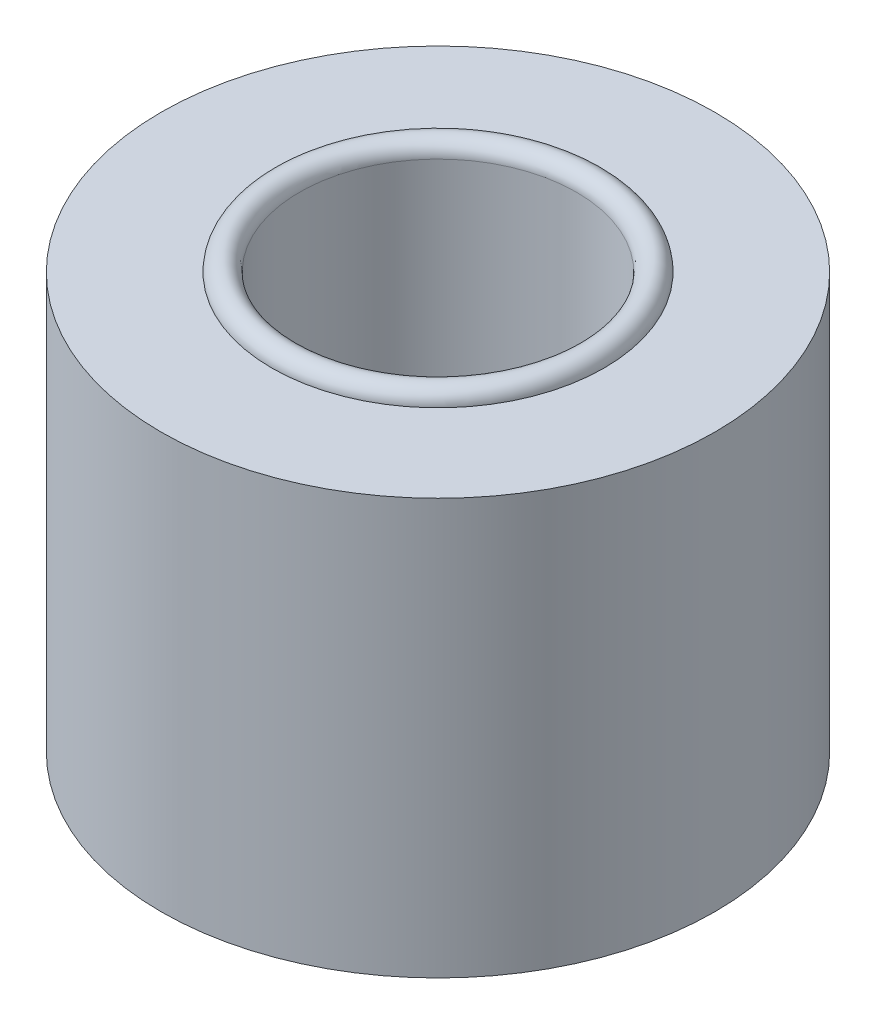
SolidWorks part; units mm, degrees
note: The reader was unsure of these and kept them because the rebuilt part matched: shared geometry of "Sketch2<2>".
ref_plane "Front Plane" through (0, 0, 0) normal (0, 0, 1) x (1, 0, 0)
ref_plane "Top Plane" through (0, 0, 0) normal (0, 1, 0) x (1, 0, 0)
ref_plane "Right Plane" through (0, 0, 0) normal (1, 0, 0) x (0, 0, -1)
sketch "Profile Sketch" plane through (0, 0, 0) normal (0, 1, 0) x (1, 0, 0)
  circle A0 centre (0, 0) radius 20
  circle A1 centre (0, 0) radius 10
  dimension "D1" = 40
  dimension "D2" = 20
extrude "Profile Extrude" add sketch "Profile Sketch" along normal blind 30
sketch "Ring Lip Profile" plane through (0, 30, 0) normal (0, 1, 0) x (1, 0, 0)
  circle A0 centre (0, 0) radius 10
  circle A1 centre (0, 0) radius 12
  circle A2 centre (0, 0) radius 10 construction
  dimension "D1" = 2
extrude "Top Ring Lip Extrude" add sketch "Ring Lip Profile" along normal blind 1
extrude "Bottom Ring Lip Extrude" add sketch "Sketch2<2>" against normal blind 1 from surface at -30 starting at face at (0, 0, 20)
sketch "Sketch2<2>" plane through (0, 30, 0) normal (0, 1, 0) x (1, 0, 0) same geometry as "Ring Lip Profile"
fillet "Top Ring Lip Fillet" radius 1 2 edges at (0, -1, 12) (0, -1, 10)
fillet "Bottom Ring Lip Fillet" radius 1 2 edges at (0, 31, 12) (0, 31, 10)
